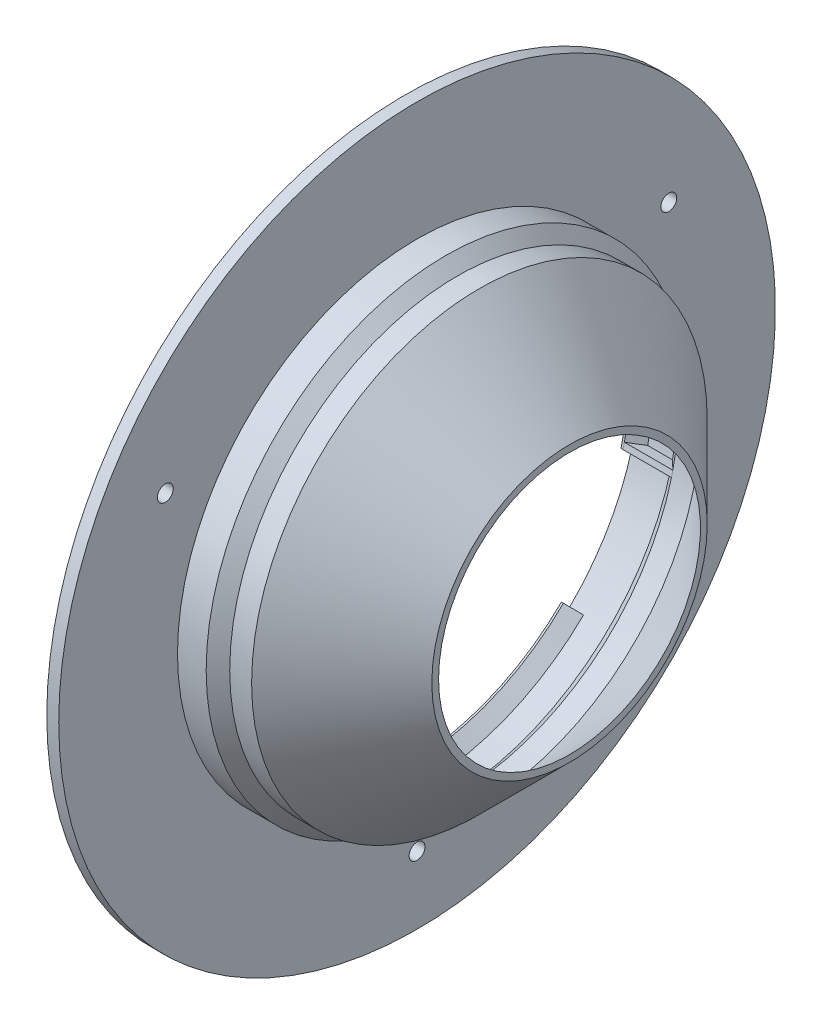
SolidWorks part; units mm, degrees
ref_plane "Alzado" through (0, 0, 0) normal (0, 0, 1) x (1, 0, 0)
ref_plane "Planta" through (0, 0, 0) normal (0, 1, 0) x (1, 0, 0)
ref_plane "Vista lateral" through (0, 0, 0) normal (1, 0, 0) x (0, 0, -1)
sketch "Croquis1" plane through (0, 0, 0) normal (0, 0, 1) x (1, 0, 0)
  line L0 (0, 56) -> (0, 90)
  line L1 (0, 90) -> (3, 90)
  line L2 (3, 90) -> (3, 60.1698)
  line L3 (3, 60.1698) -> (10.2, 60.1698)
  line L4 (10.2, 60.1698) -> (13.1571, 57.2128)
  line L5 (13.1571, 57.2128) -> (18.6571, 57.2128)
  line L6 (18.6571, 57.2128) -> (41.2845, 34.5854)
  line L7 (41.2845, 34.5854) -> (41.2845, 32.8883)
  line L8 (41.2845, 32.8883) -> (18.16, 56.0128)
  line L9 (18.16, 56.0128) -> (12.66, 56.0128)
  line L10 (12.66, 56.0128) -> (9.7029, 58.9698)
  line L11 (9.7029, 58.9698) -> (3.4698, 58.9698)
  line L12 (3.4698, 58.9698) -> (0.5, 56)
  line L13 (0.5, 56) -> (0, 56)
  line L14 (-46.0339, 0) -> (47.389, 0) construction
  dimension "D1" = 34
  dimension "D2" = 3
  dimension "D3" = 0.5
  dimension "D4" = 45
  dimension "D5" = 1.2
  dimension "D6" = 1.2
  dimension "D7" = 7.2
  dimension "D8" = 5.5
  dimension "D9" = 1.2
  dimension "D10" = 32
  dimension "D11" = 4.2
  dimension "D12" = 1.2
  dimension "D13" = 90
  dimension "D14" = 12.66
  dimension "D15" = 135
revolve "Revolución1" add sketch "Croquis1" angle 360 about L14
sketch "Croquis2" plane through (0, 0, 0) normal (-1, 0, 0) x (0, 0, 1)
  line L0 (0, 0) -> (0, 66.4177) construction
  line L1 (0, 0) -> (-14.4228, 52.007) construction
  line L2 (-14.4228, 52.007) -> (-15.759, 56.8251)
  line L3 (14.4228, 52.007) -> (15.759, 56.8251)
  line L4 (0, 0) -> (63.2199, 36.5) construction
  line L5 (52.2508, -13.513) -> (57.0915, -14.7649)
  line L6 (37.828, -38.494) -> (41.3325, -42.0603)
  line L7 (-37.828, -38.494) -> (-41.3325, -42.0603)
  line L8 (-52.2508, -13.513) -> (-57.0915, -14.7649)
  circle A1 centre (0, 0) radius 58.9698 construction
  arc A2 (-14.4228, 52.007) -> (14.4228, 52.007) centre (0, 0) cw
  arc A3 (15.759, 56.8251) -> (-15.759, 56.8251) centre (0, 0) ccw
  circle A4 centre (0, 0) radius 56 construction
  circle A5 centre (63.2199, 36.5) radius 2
  arc A6 (52.2508, -13.513) -> (37.828, -38.494) centre (0, 0) cw
  arc A7 (41.3325, -42.0603) -> (57.0915, -14.7649) centre (0, 0) ccw
  circle A8 centre (0, -73) radius 2
  arc A9 (-37.828, -38.494) -> (-52.2508, -13.513) centre (0, 0) cw
  arc A10 (-57.0915, -14.7649) -> (-41.3325, -42.0603) centre (0, 0) ccw
  circle A11 centre (-63.2199, 36.5) radius 2
  dimension "D4" = 4
  dimension "D1" = 15.5
  dimension "D2" = 73
  dimension "D3" = 60
  dimension "D6" = 5
  dimension "D5" = 3
extrude "Cortar-Extruir1" cut sketch "Croquis2" against normal blind 5
ref_axis "Eje1" through (9.7029, 0, 0) along (-1, 0, 0)
sketch "Croquis3" plane through (0, 0, 0) normal (0, -0.9681, 0.2504) x (1, 0, 0)
  line L0 (0.5, -56) -> (12.66, -56.0128)
  line L1 (12.66, -56.0128) -> (9.7029, -58.9698)
  line L2 (9.7029, -58.9698) -> (3.4698, -58.9698)
  line L3 (3.4698, -58.9698) -> (0.5, -56)
revolve "Revolución2" add sketch "Croquis3" angle 1.5 about axis through (9.7029, 0, 0) along (-1, 0, 0) reverse direction yes
sketch "Croquis4" plane through (0, 0, 0) normal (-1, 0, 0) x (0, 0, 1)
  line L0 (-54.5647, -12.5973) -> (-53.2273, 17.4027)
  arc A0 (-14.9653, 53.9633) -> (-54.2163, -14.0213) centre (0, 0) ccw construction
  dimension "D1" = 30
ref_plane "Plano1" through (0, 0, 0) normal (0, -0.9505, -0.3108) x (-1, 0, 0)
sketch "Croquis5" plane through (0, 0, 0) normal (0, -0.9505, -0.3108) x (-1, 0, 0)
  line L0 (-0.5, 56.0128) -> (-3.4698, 58.9698)
  line L1 (-3.4698, 58.9698) -> (-9.7029, 58.9698)
  line L2 (-9.7029, 58.9698) -> (-12.66, 56.0128)
  line L3 (-12.66, 56.0128) -> (-0.5, 56.0128)
  line L4 (-9.7029, -58.9698) -> (-9.7029, 58.9698) construction
  line L5 (-12.66, -56.0128) -> (-12.66, 56.0128) construction
  line L6 (-0.5, 30.9942) -> (-0.5, 56) construction
  line L7 (-3.4698, 32.6379) -> (-3.4698, 58.9698) construction
  point P2 (0, 0)
  point P9 (0, 0)
  point P14 (0, 0)
  point P16 (0, 0)
revolve "Revolución3" add sketch "Croquis5" angle 1.5 about axis through (9.7029, 0, 0) along (-1, 0, 0) reverse direction yes
pattern_circular "MatrizC1" count 3 every 120 about axis through (9.7029, 0, 0) along (-1, 0, 0) of "Revolución2", "Revolución3"
equation "\"D1@Croquis2\"=31/2"
